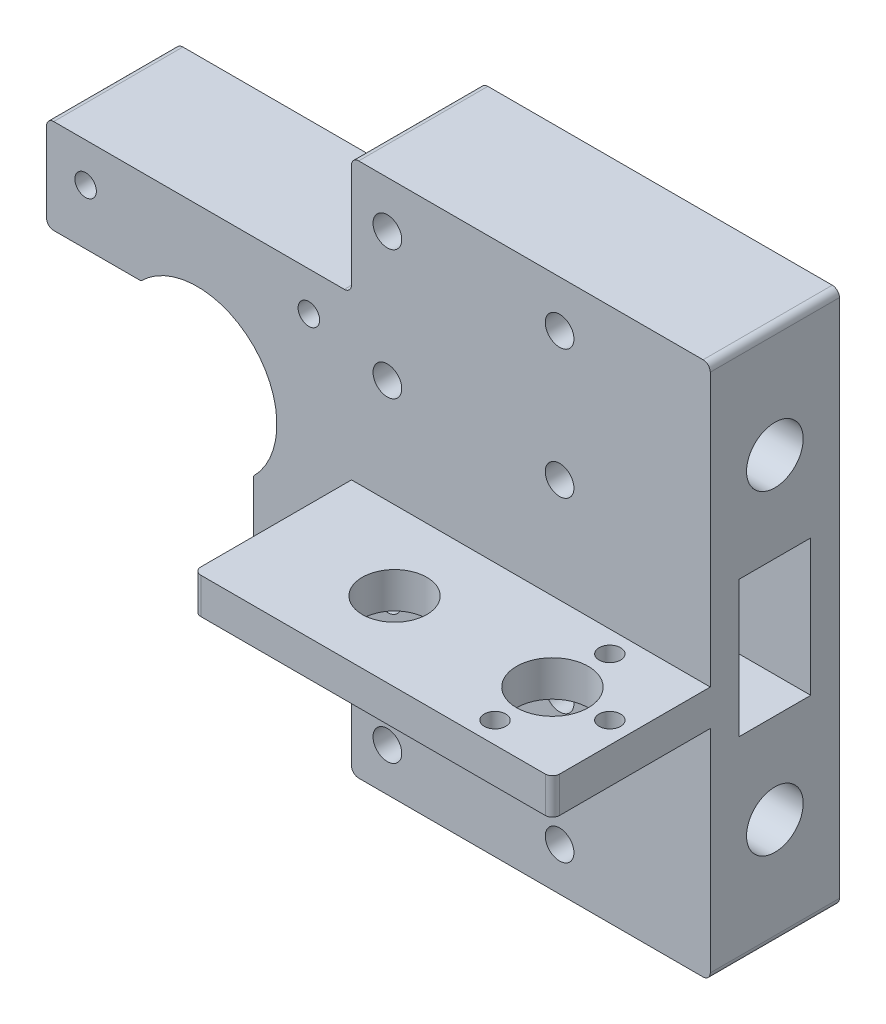
SolidWorks part; units mm, degrees
ref_plane "Front Plane" through (0, 0, 0) normal (0, 0, 1) x (1, 0, 0)
ref_plane "Top Plane" through (0, 0, 0) normal (0, 1, 0) x (1, 0, 0)
ref_plane "Right Plane" through (0, 0, 0) normal (1, 0, 0) x (0, 0, -1)
sketch "Sketch1" plane through (0, 0, 0) normal (0, 0, 1) x (1, 0, 0)
  line L0 (9, 31.6291) -> (9, -54.5727) construction
  line L1 (-25, -37) -> (25, -37)
  line L2 (-25, -37) -> (-25, 37)
  line L3 (-25, 37) -> (25, 37)
  line L4 (25, -37) -> (25, 37)
  line L5 (-25, -37) -> (25, 37) construction
  line L6 (-25, 37) -> (25, -37) construction
  line L7 (-31.7103, 0) -> (29.4717, 0) construction
  line L8 (-8, 28.8913) -> (-8, -56.8948) construction
  line L9 (-38.1073, -13) -> (73.759, -13) construction
  line L10 (-38.1073, -31) -> (69.9864, -31) construction
  line L11 (4, 28.8913) -> (4, -62.4061) construction
  line L12 (-20, 31.6291) -> (-20, -63.5871) construction
  line L13 (-32.9198, 31) -> (54.2759, 31) construction
  line L14 (-31.7103, 13) -> (56.377, 13) construction
  circle A0 centre (-20, 31) radius 2
  circle A1 centre (4, 31) radius 2
  circle A2 centre (4, 13) radius 2
  circle A3 centre (-20, 13) radius 2
  circle A4 centre (-20, -13) radius 2
  circle A5 centre (4, -13) radius 2
  circle A6 centre (4, -31) radius 2
  circle A7 centre (-20, -31) radius 2
  point P0 (0, 0)
  dimension "D11" = 4
  dimension "D1" = 74
  dimension "D2" = 50
  dimension "D3" = 34
  dimension "D4" = 17
  dimension "D5" = 12
  dimension "D6" = 12
  dimension "D7" = 18
  dimension "D8" = 6
  dimension "D9" = 18
  dimension "D10" = 6
extrude "Boss-Extrude1" add sketch "Sketch1" along normal blind 18
sketch "Sketch5" plane through (0, 37, 0) normal (0, 1, 0) x (1, 0, 0)
  line L0 (-25, -18) -> (-25, 0) construction
  line L1 (25, -18) -> (25, 0) construction
  line L2 (25, -18) -> (-25, -18) construction
  line L3 (25, 0) -> (-25, 0) construction
  line L4 (-25, -18) -> (-25, 0)
  line L5 (25, -18) -> (25, 0)
  line L6 (25, -18) -> (-25, -18)
  line L7 (25, 0) -> (-25, 0)
extrude "Boss-Extrude3" add sketch "Sketch5" along normal blind 5.5
sketch "Sketch7" plane through (0, 0, 18) normal (0, 0, 1) x (1, 0, 0)
  line L0 (25, -37) -> (25, 42.5) construction
  line L1 (-25, 42.5) -> (25, 42.5)
  line L2 (-25, 42.5) -> (-25, 37.5)
  line L3 (-25, 37.5) -> (25, 37.5)
  line L4 (25, 42.5) -> (25, 37.5)
  dimension "D1" = 5
extrude "Boss-Extrude5" add sketch "Sketch7" along normal blind 22
fillet "Fillet2" radius 1 4 edges at (25, -37, 9) (-25, -37, 9) (-25, 42.5, 20) (25, 42.5, 20)
sketch "Sketch13" plane through (25, 0, 0) normal (1, 0, 0) x (0, 0, -1)
  line L0 (-34.2555, -22) -> (22.0924, -22) construction
  line L1 (-32.2574, 22) -> (20.0943, 22) construction
  line L2 (-40, 37.5) -> (-18, 37.5) construction
  line L3 (0, -37) -> (-18, -37) construction
  line L4 (-49.0137, 0) -> (44.9027, 0) construction
  line L5 (-9, 54.631) -> (-9, -60.082) construction
  line L6 (0, -36) -> (0, 41.5) construction
  line L8 (-14, -9.5) -> (-4, -9.5)
  line L9 (-14, -9.5) -> (-14, 9.5)
  line L10 (-14, 9.5) -> (-4, 9.5)
  line L11 (-4, -9.5) -> (-4, 9.5)
  line L12 (-14, -9.5) -> (-4, 9.5) construction
  line L13 (-14, 9.5) -> (-4, -9.5) construction
  circle A0 centre (-9, 22) radius 3.95
  circle A1 centre (-9, -22) radius 3.95
  point P15 (-9, 0)
  dimension "D6" = 7.9
  dimension "D1" = 15.5
  dimension "D2" = 15
  dimension "D3" = 9
  dimension "D4" = 19
  dimension "D5" = 10
extrude "Cut-Extrude4" cut sketch "Sketch13" against normal blind 20
sketch "Sketch15" plane through (0, 42.5, 0) normal (0, 1, 0) x (1, 0, 0)
  line L0 (-8, 4.8676) -> (-8, -46.7861) construction
  line L1 (-50.585, -29) -> (48.3289, -29) construction
  line L2 (-25, -40) -> (-25, 0) construction
  line L3 (14, 11.3889) -> (14, -57.323) construction
  circle A0 centre (-8, -29) radius 4.5
  circle A1 centre (14, -29) radius 5
  dimension "D4" = 10
  dimension "D5" = 9
  dimension "D1" = 11
  dimension "D2" = 17
  dimension "D3" = 22
extrude "Cut-Extrude6" cut sketch "Sketch15" against normal blind 15
sketch "Sketch16" plane through (5, 0, 0) normal (1, 0, 0) x (0, 0, -1)
  line L0 (-14, 9.5) -> (-14, -9.5) construction
  line L1 (-14, -9.5) -> (-4, -9.5) construction
  line L2 (-4, -9.5) -> (-4, 9.5) construction
  line L3 (-4, 9.5) -> (-14, 9.5) construction
  line L4 (-14, 9.5) -> (-14, -9.5)
  line L5 (-14, -9.5) -> (-4, -9.5)
  line L6 (-4, -9.5) -> (-4, 9.5)
  line L7 (-4, 9.5) -> (-14, 9.5)
extrude "Cut-Extrude7" cut sketch "Sketch16" against normal up to next
sketch "Sketch18" plane through (5, 0, 0) normal (1, 0, 0) x (0, 0, -1)
  circle A0 centre (-9, -22) radius 3.95 construction
  circle A1 centre (-9, 22) radius 3.95 construction
  circle A2 centre (-9, -22) radius 3.95
  circle A3 centre (-9, 22) radius 3.95
extrude "Cut-Extrude8" cut sketch "Sketch18" against normal blind 8
sketch "Sketch19" plane through (0, 0, 18) normal (0, 0, 1) x (1, 0, 0)
  line L0 (0, 0) -> (-81.2446, 0) construction
  line L1 (-25, 37.5) -> (-25, -36) construction
  line L2 (-25, 21) -> (-67.5, 21)
  line L3 (-67.5, 21) -> (-67.5, 7.8489)
  line L4 (-38.6511, -24.5656) -> (-25, -24.5656)
  line L5 (-46.5, 28.9245) -> (-46.5, -35.2477) construction
  line L6 (-19.4245, 27.0755) -> (-46.5, 0) construction
  line L7 (-46.5, 0) -> (-75.2956, -28.7956) construction
  line L8 (-73.8754, 27.3754) -> (-46.5, 0) construction
  line L9 (-46.5, 0) -> (-14.9439, -31.5561) construction
  line L10 (-54.3489, 7.8489) -> (-67.5, 7.8489)
  line L11 (-38.6511, -7.8489) -> (-38.6511, -24.5656)
  circle A0 centre (-30.9437, 15.5563) radius 1.5
  circle A1 centre (-62.0563, 15.5563) radius 1.5
  arc A2 (-38.6511, -7.8489) -> (-54.3489, 7.8489) centre (-46.5, 0) ccw
  circle A3 centre (-62.0563, -15.5563) radius 1.5
  circle A4 centre (-30.9437, -15.5563) radius 1.5
  line M21 (-25, 37.5) -> (-25, -36)
  dimension "D1" = 21.5
  dimension "D2" = 22.2
  dimension "D7" = 3
  dimension "D8" = 22
  dimension "D3" = 21
  dimension "D4" = 21
  dimension "D5" = 45
  dimension "D6" = 45
  dimension "D9" = 22
  dimension "D10" = 22
  dimension "D11" = 22
extrude "Boss-Extrude6" add sketch "Sketch19" against normal up to surface (18 mm away) contours A2 L11 L4 L2 L3 L10 A4 A1 A0 M21 region at (-25.6231, -1.7828, 18) up to face at (6, -31, 0)
sketch "Sketch23" plane through (0, 42.5, 0) normal (0, 1, 0) x (1, 0, 0)
  line L0 (-25, -40) -> (-24, -40) construction
  line L1 (24, -40) -> (25, -40) construction
  line L2 (25, 0) -> (25, -40) construction
  line L3 (-25, -40) -> (-25, 0) construction
  line L4 (24, -40) -> (-24, -40) construction
  line L5 (-25, -40) -> (-24, -40)
  line L6 (24, -40) -> (25, -40)
  line L7 (25, -18) -> (25, -40)
  line L8 (-25, -40) -> (-25, -18)
  line L9 (24, -40) -> (-24, -40)
  line L10 (-25, -18) -> (25, -18)
  circle A0 centre (14, -29) radius 5 construction
  circle A1 centre (-8, -29) radius 4.5 construction
  circle A2 centre (14, -29) radius 5
  circle A3 centre (-8, -29) radius 4.5
extrude "Boss-Extrude7" add sketch "Sketch23" along normal blind 5 from offset 49 offset against normal yes
sketch "Sketch24" plane through (0, 0, 40) normal (0, 0, 1) x (1, 0, 0)
  line L0 (25, 37.5) -> (25, 41.5) construction
  line L1 (-25, 37.5) -> (25, 37.5) construction
  line L2 (-25, 41.5) -> (-25, 37.5) construction
  line L3 (24, 42.5) -> (-24, 42.5) construction
  line L4 (25, 37.5) -> (25, 41.5)
  line L5 (-25, 37.5) -> (25, 37.5)
  line L6 (-25, 41.5) -> (-25, 37.5)
  line L7 (24, 42.5) -> (-24, 42.5)
  arc A0 (25, 41.5) -> (24, 42.5) centre (24, 41.5) ccw construction
  arc A1 (-24, 42.5) -> (-25, 41.5) centre (-24, 41.5) ccw construction
  arc A2 (25, 41.5) -> (24, 42.5) centre (24, 41.5) ccw
  arc A3 (-24, 42.5) -> (-25, 41.5) centre (-24, 41.5) ccw
extrude "Cut-Extrude9" cut sketch "Sketch24" against normal up to next
sketch "Sketch25" plane through (-25, 0, 0) normal (1, 0, 0) x (0, 0, -1)
  line L0 (-4, -9.5) -> (-14, -9.5) construction
  line L1 (-14, 9.5) -> (-14, -9.5) construction
  line L2 (-14, 9.5) -> (-4, 9.5) construction
  line L3 (-4, 9.5) -> (-4, -9.5) construction
  line L4 (-4, -9.5) -> (-14, -9.5)
  line L5 (-14, 9.5) -> (-14, -9.5)
  line L6 (-14, 9.5) -> (-4, 9.5)
  line L7 (-4, 9.5) -> (-4, -9.5)
extrude "Cut-Extrude10" cut sketch "Sketch25" against normal up to next
fillet "Fillet3" radius 1 9 edges at (-38.6511, -24.5656, 9) (-25, -24.5656, 9) (-25, 21, 9) (-67.5, 7.8489, 9) (-67.5, 21, 9) (25, -4, 40) (-25, -4, 40) (25, 37.5, 9) (-25, 37.5, 9) first distance on face at (-31.8256, -24.5656, 9) first distance on face at (-25, -30.2828, 9) first distance on face at (-25, 29.25, 9) first distance on face at (-67.5, 14.4244, 9) first distance on face at (25, 22, 5.05) first distance on face at (-25, -4, 29)
sketch "Sketch26" plane through (0, -1.5, 0) normal (0, 1, 0) x (1, 0, 0)
  line L0 (1.4046, -29) -> (36.084, -29) construction
  line L1 (14, -38.7516) -> (14, -16.0575) construction
  circle A0 centre (14, -21) radius 1.5
  circle A1 centre (22, -29) radius 1.5
  circle A2 centre (14, -37) radius 1.5
  circle A3 centre (14, -29) radius 5 construction
  dimension "D1" = 3
  dimension "D3" = 8
  dimension "D4" = 8
  dimension "D2" = 8
extrude "Cut-Extrude11" cut sketch "Sketch26" against normal up to next
